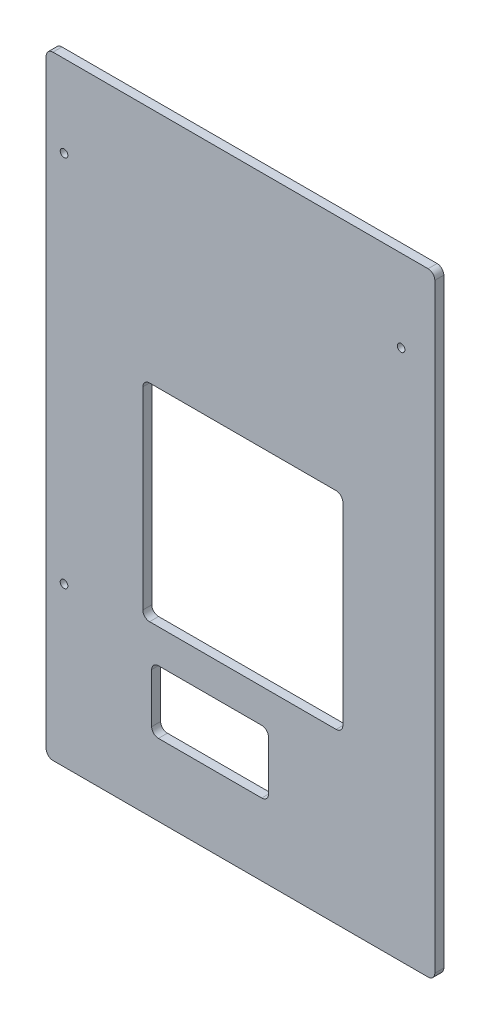
SolidWorks part; units mm, degrees
material "Verre"
ref_plane "Plan de face" through (0, 0, 0) normal (0, 0, 1) x (1, 0, 0)
ref_plane "Plan de dessus" through (0, 0, 0) normal (0, 1, 0) x (1, 0, 0)
ref_plane "Plan de droite" through (0, 0, 0) normal (1, 0, 0) x (0, 0, -1)
sketch "Esquisse1" plane through (0, 0, 0) normal (0, 0, 1) x (1, 0, 0)
  line L1 (0, 0) -> (172.93, 0)
  line L2 (0, 0) -> (0, 273)
  line L3 (0, 273) -> (172.93, 273)
  line L4 (172.93, 0) -> (172.93, 273)
  line L5 (43, 75) -> (132, 75)
  line L6 (43, 75) -> (43, 167)
  line L7 (43, 167) -> (132, 167)
  line L8 (132, 75) -> (132, 167)
  line L9 (46.93, 60) -> (98.93, 60)
  line L10 (46.93, 60) -> (46.93, 32)
  line L11 (46.93, 32) -> (98.93, 32)
  line L12 (98.93, 60) -> (98.93, 32)
  circle A0 centre (7.93, 236.5) radius 1.5
  circle A1 centre (7.93, 70.5) radius 1.5
  circle A2 centre (157.93, 236.5) radius 1.5
  dimension "D8" = 3
  dimension "D10" = 3
  dimension "D14" = 3
  dimension "D1" = 172.93
  dimension "D2" = 273
  dimension "D3" = 43
  dimension "D4" = 89
  dimension "D5" = 92
  dimension "D6" = 15
  dimension "D7" = 7.93
  dimension "D9" = 7.93
  dimension "D11" = 36.5
  dimension "D12" = 70.5
  dimension "D13" = 36.5
  dimension "D15" = 15
  dimension "D16" = 74
  dimension "D17" = 28
  dimension "D18" = 32
  dimension "D19" = 52
extrude "Boss.-Extru.1" add sketch "Esquisse1" along normal blind 4
fillet "Congé1" radius 3 12 edges at (0, 0, 2) (172.93, 0, 2) (172.93, 273, 2) (0, 273, 2) (43, 75, 2) (132, 75, 2) (132, 167, 2) (43, 167, 2) (98.93, 32, 2) (46.93, 32, 2) (98.93, 60, 2) (46.93, 60, 2)
hole_wizard "Dégagement M31" positions "Esquisse2" profile "Esquisse3" hole size "M3" standard "ISO" end condition through all
sketch "Esquisse2" plane through (0, 0, 4) normal (0, 0, 1) x (1, 0, 0)
  point P0 (7.93, 236.5)
  point P3 (7.93, 70.5)
  point P6 (157.93, 236.5)
sketch "Esquisse3" plane through (7.93, 236.5, 4) normal (1, 0, 0) x (0, -1, 0)
  line L0 (0, 0) -> (0, 4)
  line L1 (0, 4) -> (1.7, 4)
  line L2 (1.7, 4) -> (1.7, 0)
  line L5 (1.7, 0) -> (0, 0)
  line L11 (0, -6.35) -> (0, 107.95) construction
  dimension "Diamètre du perçage jusqu'au prochain" = 3.4
  dimension "Profondeur du perçage jusqu'au prochain" = 4
